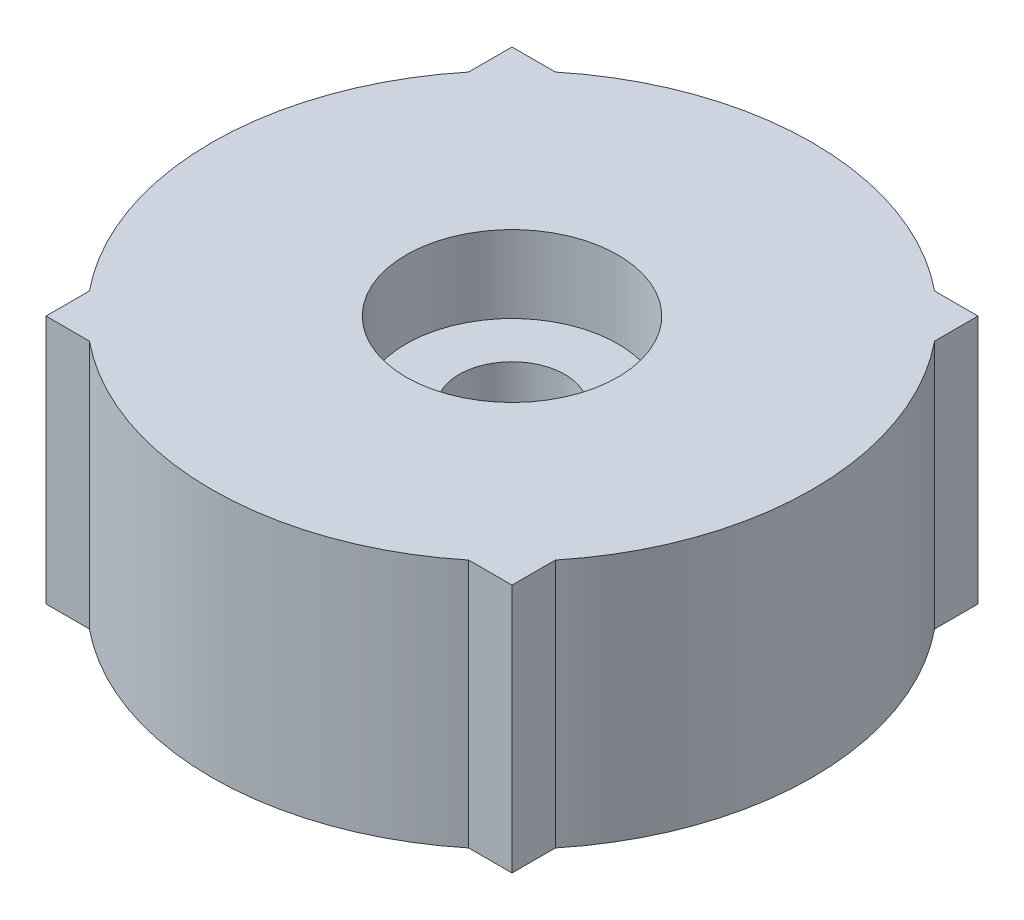
SolidWorks part; units mm, degrees
ref_plane "Front Plane" through (0, 0, 0) normal (0, 0, 1) x (1, 0, 0)
ref_plane "Top Plane" through (0, 0, 0) normal (0, 1, 0) x (1, 0, 0)
ref_plane "Right Plane" through (0, 0, 0) normal (1, 0, 0) x (0, 0, -1)
sketch "Sketch1" plane through (0, 0, 0) normal (0, 1, 0) x (1, 0, 0)
  line L1 (-3.7, -3.7) -> (3.7, -3.7)
  line L2 (-3.7, -3.7) -> (-3.7, 3.7)
  line L3 (-3.7, 3.7) -> (3.7, 3.7)
  line L4 (3.7, -3.7) -> (3.7, 3.7)
  line L5 (-3.7, -3.7) -> (3.7, 3.7) construction
  line L6 (-3.7, 3.7) -> (3.7, -3.7) construction
  circle A0 centre (0, 0) radius 1.375
  point P0 (0, 0)
  dimension "D3" = 2.75
  dimension "D1" = 7.4
  dimension "D2" = 7.4
extrude "Boss-Extrude1" add sketch "Sketch1" along normal blind 2
sketch "Sketch2" plane through (0, 2, 0) normal (0, 1, 0) x (1, 0, 0)
  line L1 (-5.05, -5.05) -> (5.05, -5.05)
  line L2 (-5.05, -5.05) -> (-5.05, 5.05)
  line L3 (-5.05, 5.05) -> (5.05, 5.05)
  line L4 (5.05, -5.05) -> (5.05, 5.05)
  line L5 (-5.05, -5.05) -> (5.05, 5.05) construction
  line L6 (-5.05, 5.05) -> (5.05, -5.05) construction
  line L7 (-6.05, -6.05) -> (6.05, -6.05)
  line L8 (-6.05, -6.05) -> (-6.05, 6.05)
  line L9 (-6.05, 6.05) -> (6.05, 6.05)
  line L10 (6.05, -6.05) -> (6.05, 6.05)
  line L11 (-6.05, -6.05) -> (6.05, 6.05) construction
  line L12 (-6.05, 6.05) -> (6.05, -6.05) construction
  point P0 (0, 0)
  point P6 (0, 0)
  dimension "D1" = 10.1
  dimension "D2" = 10.1
  dimension "D3" = 12.1
extrude "Boss-Extrude2" add sketch "Sketch2" against normal up to surface (2 mm away) separate body up to face at (0, 0, 0)
sketch "Sketch3" plane through (0, 2, 0) normal (0, 1, 0) x (1, 0, 0)
  line L1 (-6.05, -6.05) -> (6.05, -6.05)
  line L2 (-6.05, -6.05) -> (-6.05, 6.05)
  line L3 (-6.05, 6.05) -> (6.05, 6.05)
  line L4 (6.05, -6.05) -> (6.05, 6.05)
  line L5 (-6.05, -6.05) -> (6.05, 6.05) construction
  line L6 (-6.05, 6.05) -> (6.05, -6.05) construction
  circle A0 centre (0, 0) radius 2.75
  point P0 (0, 0)
  dimension "D1" = 5.5
extrude "Boss-Extrude3" add sketch "Sketch3" along normal blind 2 contours A0 | L2 L1 L4 L3
sketch "Sketch4" plane through (0, 2, 0) normal (0, 1, 0) x (1, 0, 0)
  line L0 (0, 0) -> (0, -20) construction
  line L1 (4, 0) -> (4, -20)
  line L2 (-4, 0) -> (-4, -20)
  arc A0 (4, 0) -> (-4, 0) centre (0, 0) ccw
  arc A1 (-4, -20) -> (4, -20) centre (0, -20) ccw
  circle A2 centre (0, 0) radius 1.375
  circle A3 centre (0, 0) radius 2.75
  circle A4 centre (0, -20) radius 1.675
  point P3 (0, -10)
  circle M7 centre (0, 0) radius 2.75
  dimension "D1" = 4
  dimension "D3" = 3.35
  dimension "D2" = 20
extrude "Boss-Extrude4" add sketch "Sketch4" along normal blind 2 contours L2 A1 L1 A0 A4 M7 region at (0, 2, 10.841)
sketch "Sketch5" plane through (0, 2, 0) normal (0, -1, 0) x (-1, 0, 0)
  line L0 (4, -20) -> (4, -6.05)
  line L1 (4, -6.05) -> (-4, -6.05)
  line L2 (-4, -6.05) -> (-4, -20)
  circle A0 centre (0, -20) radius 1.675
  circle A1 centre (0, -20) radius 4
  circle M3 centre (0, -20) radius 1.675
  line M4 (4, -20) -> (4, -6.05)
  line M5 (4, -6.05) -> (-4, -6.05)
  line M6 (-4, -6.05) -> (-4, -20)
  arc M7 (-4, -20) -> (4, -20) centre (0, -20) ccw
extrude "Boss-Extrude5" add sketch "Sketch5" along normal blind 1.3 contours A1 M4 M5 M6 | A1 M7 M3 region at (0, 2, 11.4911) region at (0, 2, 23.8869)
sketch "Sketch10" plane through (0, 0.7, 0) normal (0, -1, 0) x (1, 0, 0)
  line L1 (-5.05, -5.05) -> (5.05, -5.05)
  line L2 (-5.05, -5.05) -> (-5.05, 5.05)
  line L3 (-5.05, 5.05) -> (5.05, 5.05)
  line L4 (5.05, -5.05) -> (5.05, 5.05)
  line L5 (-5.05, -5.05) -> (5.05, 5.05) construction
  line L6 (-5.05, 5.05) -> (5.05, -5.05) construction
  line L7 (-6.05, -6.05) -> (6.05, -6.05)
  line L8 (-6.05, -6.05) -> (-6.05, 6.05)
  line L9 (-6.05, 6.05) -> (6.05, 6.05)
  line L10 (6.05, -6.05) -> (6.05, 6.05)
  line L11 (-6.05, -6.05) -> (6.05, 6.05) construction
  line L12 (-6.05, 6.05) -> (6.05, -6.05) construction
  point P0 (0, 0)
  point P7 (0, 0)
extrude "Boss-Extrude6" add sketch "Sketch10" along normal blind 3.175
sketch "Sketch11" plane through (0, 0.7, 0) normal (0, -1, 0) x (-1, 0, 0)
  line L1 (4, -6.05) -> (-4.881, -6.05)
  line L2 (4, -6.05) -> (4, -24.1435)
  line L3 (4, -24.1435) -> (-4.881, -24.1435)
  line L4 (-4.881, -6.05) -> (-4.881, -24.1435)
extrude "Cut-Extrude1" cut sketch "Sketch11" against normal blind 10
sketch "Sketch14" plane through (0, -2.475, 0) normal (0, -1, 0) x (-1, 0, 0)
  line L1 (6.05, 6.05) -> (-6.05, 6.05)
  line L2 (6.05, 6.05) -> (6.05, -6.05)
  line L3 (6.05, -6.05) -> (-6.05, -6.05)
  line L4 (-6.05, 6.05) -> (-6.05, -6.05)
  circle A0 centre (0, 0) radius 7.8
  line M10 (-5.05, -5.05) -> (-5.05, 5.05)
  line M11 (-5.05, 5.05) -> (5.05, 5.05)
  line M12 (5.05, 5.05) -> (5.05, -5.05)
  line M13 (5.05, -5.05) -> (-5.05, -5.05)
  dimension "D1" = 15.6
extrude "Boss-Extrude7" add sketch "Sketch14" against normal up to surface (6.475 mm away) contours L1 A0 | L2 A0 | M10 M13 M12 M11 | A0 region at (0, -2.475, -6.7572) region at (-6.7572, -2.475, 0) region at (0, -2.475, 0) up to face at (0, 4, 0)
